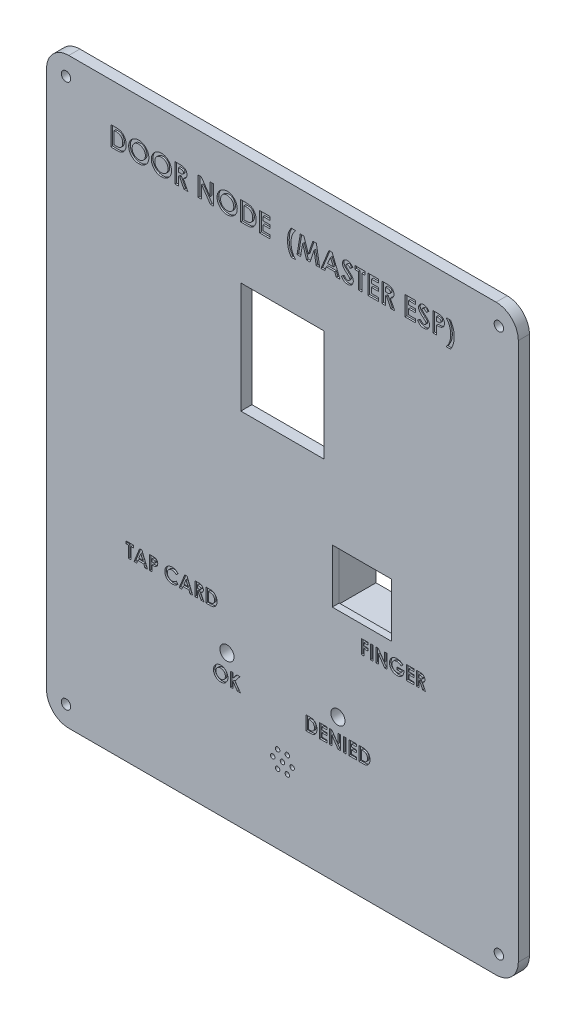
SolidWorks part; units mm, degrees
ref_plane "Front Plane" through (0, 0, 0) normal (0, 0, 1) x (1, 0, 0)
ref_plane "Top Plane" through (0, 0, 0) normal (0, 1, 0) x (1, 0, 0)
ref_plane "Right Plane" through (0, 0, 0) normal (1, 0, 0) x (0, 0, -1)
sketch "Sketch1" plane through (0, 0, 0) normal (0, 0, 1) x (1, 0, 0)
  line L0 (-77, 0) -> (77, 0)
  line L1 (85, 8) -> (85, 202)
  line L2 (77, 210) -> (-77, 210)
  line L3 (-85, 202) -> (-85, 8)
  arc A0 (-85, 8) -> (-77, 0) centre (-77, 8) ccw
  arc A1 (77, 0) -> (85, 8) centre (77, 8) ccw
  arc A2 (85, 202) -> (77, 210) centre (77, 202) ccw
  arc A3 (-77, 210) -> (-85, 202) centre (-77, 202) ccw
extrude "Panel" add sketch "Sketch1" along normal blind 4
ref_plane "P1_Front_4" through (0, 0, 4) normal (0, 0, 1) x (1, 0, 0)
sketch "Sketch2" plane through (0, 0, 0) normal (0, 0, 1) x (1, 0, 0)
  circle A0 centre (-78, 7) radius 1.7
  circle A1 centre (78, 7) radius 1.7
  circle A2 centre (-78, 203) radius 1.7
  circle A3 centre (78, 203) radius 1.7
extrude "Screw holes" cut sketch "Sketch2" along normal through all
ref_plane "P2_Front_-3" through (0, 0, -3) normal (0, 0, 1) x (1, 0, 0)
sketch "Sketch3" plane through (0, 0, -3) normal (0, 0, 1) x (1, 0, 0)
  line L1 (-15, 3.3) -> (15, 3.3)
  line L2 (-15, 3.3) -> (-15, 5.3)
  line L3 (-15, 5.3) -> (15, 5.3)
  line L4 (15, 3.3) -> (15, 5.3)
  line L6 (-15, 204.7) -> (15, 204.7)
  line L7 (-15, 204.7) -> (-15, 206.7)
  line L8 (-15, 206.7) -> (15, 206.7)
  line L9 (15, 204.7) -> (15, 206.7)
  line L11 (-81.7, 90) -> (-79.7, 90)
  line L12 (-81.7, 90) -> (-81.7, 120)
  line L13 (-81.7, 120) -> (-79.7, 120)
  line L14 (-79.7, 90) -> (-79.7, 120)
  line L16 (79.7, 90) -> (81.7, 90)
  line L17 (79.7, 90) -> (79.7, 120)
  line L18 (79.7, 120) -> (81.7, 120)
  line L19 (81.7, 90) -> (81.7, 120)
extrude "Locating tabs" add sketch "Sketch3" along normal blind 3
sketch "Sketch4" plane through (0, 0, 0) normal (0, 0, 1) x (1, 0, 0)
  line L1 (-15, 130) -> (15, 130)
  line L2 (-15, 130) -> (-15, 170)
  line L3 (-15, 170) -> (15, 170)
  line L4 (15, 130) -> (15, 170)
  line L5 (-15, 130) -> (15, 170) construction
  line L6 (-15, 170) -> (15, 130) construction
extrude "TFT window" cut sketch "Sketch4" along normal through all
ref_plane "P3_Front_-2.4" through (0, 0, -2.4) normal (0, 0, 1) x (1, 0, 0)
sketch "Sketch5" plane through (0, 0, -2.4) normal (0, 0, 1) x (1, 0, 0)
  circle A0 centre (-14.25, 124) radius 2.1
  circle A1 centre (-14.25, 176) radius 2.1
  circle A2 centre (14.25, 124) radius 2.1
  circle A3 centre (14.25, 176) radius 2.1
extrude "TFT bosses" add sketch "Sketch5" along normal blind 2.4
ref_plane "P4_Front_-2.4" through (0, 0, -2.4) normal (0, 0, 1) x (1, 0, 0)
sketch "Sketch6" plane through (0, 0, -2.4) normal (0, 0, 1) x (1, 0, 0)
  circle A0 centre (-14.25, 124) radius 1.1
  circle A1 centre (-14.25, 176) radius 1.1
  circle A2 centre (14.25, 124) radius 1.1
  circle A3 centre (14.25, 176) radius 1.1
extrude "TFT pilot holes" cut sketch "Sketch6" along normal blind 4
sketch "Sketch7" plane through (0, 0, 0) normal (0, 0, 1) x (1, 0, 0)
  line L1 (-61.8, 74.3) -> (-18.2, 74.3)
  line L2 (-61.8, 74.3) -> (-61.8, 115.7)
  line L3 (-61.8, 115.7) -> (-18.2, 115.7)
  line L4 (-18.2, 74.3) -> (-18.2, 115.7)
  line L5 (-61.8, 74.3) -> (-18.2, 115.7) construction
  line L6 (-61.8, 115.7) -> (-18.2, 74.3) construction
  circle A0 centre (-53.9, 82.4) radius 3
  circle A1 centre (-53.9, 107.6) radius 3
  circle A2 centre (-26.1, 82.4) radius 3
  circle A3 centre (-26.1, 107.6) radius 3
extrude "NFC pocket" cut sketch "Sketch7" along normal blind 2.5
sketch "Sketch8" plane through (0, 0, 0) normal (0, 0, 1) x (1, 0, 0)
  circle A0 centre (-53.9, 82.4) radius 1.1
  circle A1 centre (-53.9, 107.6) radius 1.1
  circle A2 centre (-26.1, 82.4) radius 1.1
  circle A3 centre (-26.1, 107.6) radius 1.1
extrude "NFC pilot holes" cut sketch "Sketch8" along normal blind 3
sketch "Sketch9" plane through (0, 0, 4) normal (0, 0, 1) x (1, 0, 0)
  line L1 (-64.8, 71.3) -> (-15.2, 71.3)
  line L2 (-64.8, 71.3) -> (-64.8, 118.7)
  line L3 (-64.8, 118.7) -> (-15.2, 118.7)
  line L4 (-15.2, 71.3) -> (-15.2, 118.7)
  line L5 (-64.8, 71.3) -> (-15.2, 118.7) construction
  line L6 (-64.8, 118.7) -> (-15.2, 71.3) construction
extrude "NFC tap outline recess" cut sketch "Sketch9" against normal blind 0.6
ref_plane "P5_Front_3.4" through (0, 0, 3.4) normal (0, 0, 1) x (1, 0, 0)
sketch "Sketch10" plane through (0, 0, 3.4) normal (0, 0, 1) x (1, 0, 0)
  line L0 (-15.2, 118.7) -> (-64.8, 118.7) construction
  line L1 (-64.8, 71.3) -> (-15.2, 71.3)
  line L2 (-64.8, 71.3) -> (-64.8, 118.7)
  line L3 (-64.8, 118.7) -> (-15.2, 118.7)
  line L4 (-15.2, 71.3) -> (-15.2, 118.7)
  line L5 (-64.8, 71.3) -> (-15.2, 118.7) construction
  line L6 (-64.8, 118.7) -> (-15.2, 71.3) construction
  point P0 (-40, 95)
extrude "NFC tap outline fill" add sketch "Sketch10" along normal blind 0.6
sketch "Sketch11" plane through (0, 0, 0) normal (0, 0, 1) x (1, 0, 0)
  line L1 (17.7, 84.75) -> (62.3, 84.75)
  line L2 (17.7, 84.75) -> (17.7, 105.25)
  line L3 (17.7, 105.25) -> (62.3, 105.25)
  line L4 (62.3, 84.75) -> (62.3, 105.25)
  line L5 (17.7, 84.75) -> (62.3, 105.25) construction
  line L6 (17.7, 105.25) -> (62.3, 84.75) construction
extrude "Fingerprint pocket" cut sketch "Sketch11" along normal blind 1.5
sketch "Sketch12" plane through (0, 0, 0) normal (0, 0, 1) x (1, 0, 0)
  line L1 (17.95, 85.3) -> (39.35, 85.3)
  line L2 (17.95, 85.3) -> (17.95, 104.7)
  line L3 (17.95, 104.7) -> (39.35, 104.7)
  line L4 (39.35, 85.3) -> (39.35, 104.7)
  line L5 (17.95, 85.3) -> (39.35, 104.7) construction
  line L6 (17.95, 104.7) -> (39.35, 85.3) construction
extrude "Fingerprint aperture" cut sketch "Sketch12" along normal through all
ref_plane "P6_Front_-12" through (0, 0, -12) normal (0, 0, 1) x (1, 0, 0)
sketch "Sketch13" plane through (0, 0, -12) normal (0, 0, 1) x (1, 0, 0)
  line L1 (15.7, 105.25) -> (62.3, 105.25)
  line L2 (15.7, 105.25) -> (15.7, 107.25)
  line L3 (15.7, 107.25) -> (62.3, 107.25)
  line L4 (62.3, 105.25) -> (62.3, 107.25)
  line L6 (15.7, 82.75) -> (62.3, 82.75)
  line L7 (15.7, 82.75) -> (15.7, 84.75)
  line L8 (15.7, 84.75) -> (62.3, 84.75)
  line L9 (62.3, 82.75) -> (62.3, 84.75)
extrude "Fingerprint cradle sides" add sketch "Sketch13" along normal blind 12
ref_plane "P7_Front_-12" through (0, 0, -12) normal (0, 0, 1) x (1, 0, 0)
sketch "Sketch14" plane through (0, 0, -12) normal (0, 0, 1) x (1, 0, 0)
  line L1 (15.7, 84.75) -> (17.7, 84.75)
  line L2 (15.7, 84.75) -> (15.7, 105.25)
  line L3 (15.7, 105.25) -> (17.7, 105.25)
  line L4 (17.7, 84.75) -> (17.7, 105.25)
extrude "Fingerprint cradle end" add sketch "Sketch14" along normal blind 12
ref_plane "P8_Top_108.25" through (0, 108.25, 0) normal (0, 1, 0) x (1, 0, 0)
sketch "Sketch15" plane through (0, 108.25, 0) normal (0, 1, 0) x (1, 0, 0)
  line L1 (28, 8) -> (32, 8)
  line L2 (28, 8) -> (28, 10.5)
  line L3 (28, 10.5) -> (32, 10.5)
  line L4 (32, 8) -> (32, 10.5)
  line L5 (28, 8) -> (32, 10.5) construction
  line L6 (28, 10.5) -> (32, 8) construction
extrude "Fingerprint tie slots" cut sketch "Sketch15" against normal through all
sketch "Sketch16" plane through (0, 0, 0) normal (0, 0, 1) x (1, 0, 0)
  circle A0 centre (-20, 52) radius 2.55
  circle A1 centre (20, 52) radius 2.55
extrude "LED holes" cut sketch "Sketch16" along normal through all
sketch "Sketch17" plane through (0, 0, 0) normal (0, 0, 1) x (1, 0, 0)
  circle A0 centre (0, 28) radius 0.8
  circle A1 centre (3.5, 28) radius 0.8
  circle A2 centre (1.75, 31.0311) radius 0.8
  circle A3 centre (-1.75, 31.0311) radius 0.8
  circle A4 centre (-3.5, 28) radius 0.8
  circle A5 centre (-1.75, 24.9689) radius 0.8
  circle A6 centre (1.75, 24.9689) radius 0.8
extrude "Buzzer sound holes" cut sketch "Sketch17" along normal through all
ref_plane "P9_Front_-7" through (0, 0, -7) normal (0, 0, 1) x (1, 0, 0)
sketch "Sketch18" plane through (0, 0, -7) normal (0, 0, 1) x (1, 0, 0)
  circle A0 centre (0, 28) radius 7.85
  circle A1 centre (0, 28) radius 6.25
extrude "Buzzer cradle" add sketch "Sketch18" along normal blind 7
sketch "Sketch19" plane through (0, 0, 4) normal (0, 0, 1) x (1, 0, 0)
  text T0 "DOOR NODE  (MASTER ESP)" font "Century Gothic" height 7
  text T1 "TAP CARD" font "Century Gothic" height 5
  text T2 "FINGER" font "Century Gothic" height 5
  text T3 "OK" font "Century Gothic" height 5
  text T4 "DENIED" font "Century Gothic" height 5
extrude "Labels (engraved)" cut sketch "Sketch19" against normal blind 0.6
